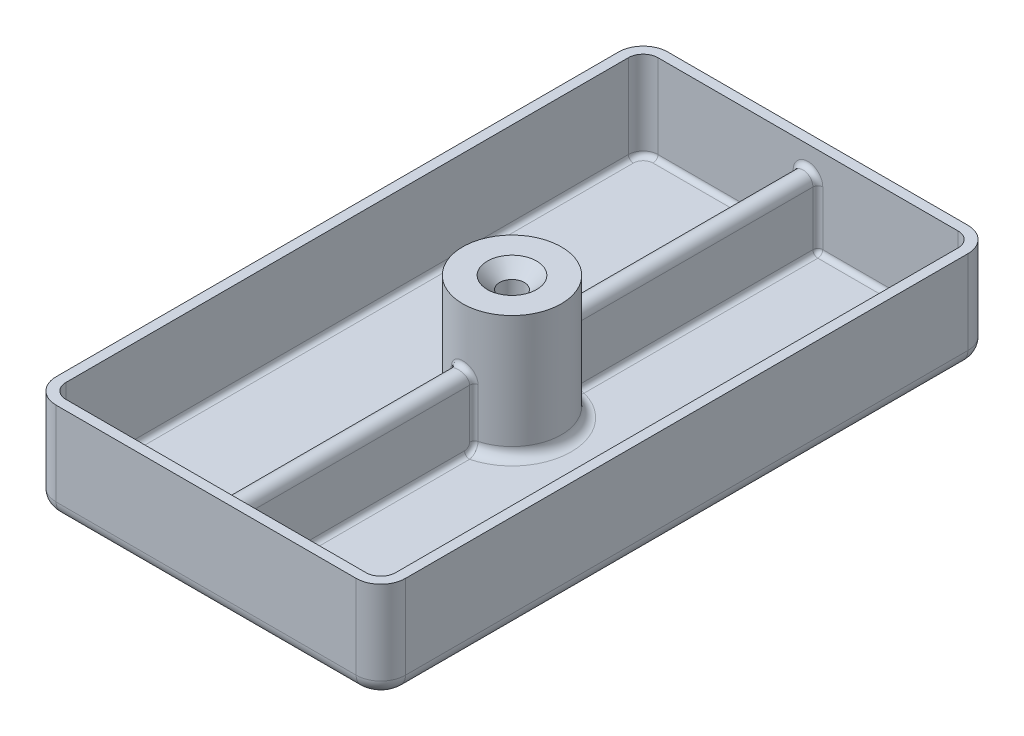
SolidWorks part; units mm, degrees
material "PW20:29:Sc:0:"
ref_plane "Front" through (0, 0, 0) normal (0, 0, 1) x (1, 0, 0)
ref_plane "Top" through (0, 0, 0) normal (0, 1, 0) x (1, 0, 0)
ref_plane "Right" through (0, 0, 0) normal (1, 0, 0) x (0, 0, -1)
sketch "Sketch1" plane through (0, 0, 0) normal (0, 1, 0) x (1, 0, 0)
  line L0 (-35.4102, -62.0052) -> (35.4102, -62.0052)
  line L1 (-35.4102, -62.0052) -> (-35.4102, 62.0052)
  line L2 (35.4102, 62.0052) -> (-35.4102, 62.0052)
  line L3 (35.4102, 62.0052) -> (35.4102, -62.0052)
  line L4 (-35.4102, 62.0052) -> (35.4102, -62.0052) construction
  point P5 (0, 0)
  dimension "D1" = 124.0104
  dimension "D2" = 70.8205
extrude "Base-Extrude" add sketch "Sketch1" along normal blind 20
fillet "Fillet1" radius 5 4 edges at (-35.4102, 10, -62.0052) (-35.4102, 10, 62.0052) (35.4102, 10, 62.0052) (35.4102, 10, -62.0052)
fillet "Fillet2" radius 3 8 edges at (35.4102, 0, 0) (33.9458, 0, 60.5407) (33.9458, 0, -60.5407) (0, 0, 62.0052) (0, 0, -62.0052) (-33.9458, 0, 60.5407) (-33.9458, 0, -60.5407) (-35.4102, 0, 0)
shell "Shell1" thickness 2 removed face at (0, 20, 0)
sketch "Sketch2" plane through (0, 0, 0) normal (0, 0, 1) x (1, 0, 0)
  line L0 (0, 0) -> (0, 23.9525) construction
  line L1 (-2, 2) -> (-2, 14)
  line L2 (30.4102, 2) -> (-30.4102, 2) construction
  line L3 (2, 14) -> (2, 2)
  line L4 (2, 2) -> (-2, 2)
  arc A0 (-2, 14) -> (2, 14) centre (0, 14) cw
  dimension "D1" = 2
  dimension "D2" = 12
extrude "Rib" add sketch "Sketch2" along normal up to next and the other way up to next
sketch "Sketch3" plane through (0, 2, 0) normal (0, 1, 0) x (-1, 0, 0)
  circle A0 centre (0, 0) radius 10
  dimension "D1" = 20
extrude "CylBoss" add sketch "Sketch3" along normal blind 25
fillet "Fillet4" radius 2 2 edges at (10, 2, 0) (-10, 2, 0)
fillet "Fillet5" radius 1 24 edges at (-2, 8.5, 60.0052) (-2, 8.5, -60.0052) (0, 16, 60.0052) (-2, 2.2929, 59.7123) (-2, 2.2929, -59.7123) (0, 16, -60.0052) (2, 8.5, 60.0052) (-2, 2, 35.4187) (-2, 2, -35.4187) (2, 8.5, -60.0052) (2, 2.2929, 59.7123) (-2, 2.7686, 10.2304) (-2, 2.4508, -10.5472) (2, 2.2929, -59.7123) (2, 2, 35.4187) (-2, 9, 9.798) (-2, 9, -9.798) (2, 2, -35.4187) (2, 2.4508, 10.5472) (-0.455, 12.0524, 9.9896) (-0.455, 15.9476, -9.9896) (2, 2.7686, -10.2304) (2, 9, 9.798) (2, 9, -9.798)
hole_wizard "CounterSnk" positions "Sketch4" profile "Sketch5" legacy end condition through all
sketch "Sketch4" plane through (0, 27, 0) normal (0, 1, 0) x (-1, 0, 0)
  point P0 (0, 0)
sketch "Sketch5" plane through (0, 27, 0) normal (1, 0, 0) x (0, 0, 1)
  line L0 (0, 0) -> (0, 27)
  line L1 (0, 27) -> (2.5, 27)
  line L2 (2.5, 27) -> (2.5, 2.5)
  line L3 (2.5, 2.5) -> (5, 0)
  line L4 (5, 0) -> (0, 0)
  line L5 (0, 116.4889) -> (0, 0) construction
